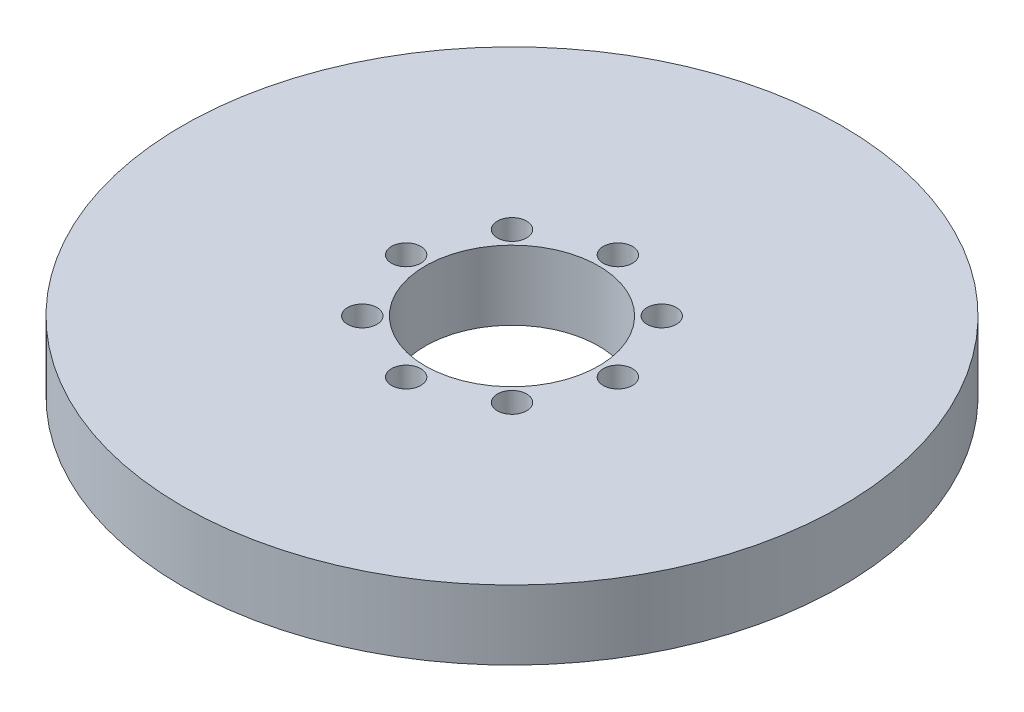
SolidWorks part; units mm, degrees
ref_plane "Front Plane" through (0, 0, 0) normal (0, 0, 1) x (1, 0, 0)
ref_plane "Top Plane" through (0, 0, 0) normal (0, 1, 0) x (1, 0, 0)
ref_plane "Right Plane" through (0, 0, 0) normal (1, 0, 0) x (0, 0, -1)
sketch "Sketch1" plane through (0, 0, 0) normal (0, 1, 0) x (1, 0, 0)
  circle A0 centre (0, 0) radius 47.5
  dimension "FLANGE_OD" = 95
extrude "Boss-Extrude1" add sketch "Sketch1" along normal blind 10
sketch "Sketch2" plane through (0, 0, 0) normal (0, 1, 0) x (1, 0, 0)
  circle A0 centre (0, 0) radius 12.5
  dimension "BORE_D" = 25
extrude "Cut-Extrude1" cut sketch "Sketch2" along normal through all
sketch "Sketch3" plane through (0, 10, 0) normal (0, 1, 0) x (1, 0, 0)
  circle A0 centre (0, 0) radius 15.2597 construction
  circle A1 centre (-15.2597, 0) radius 2.11
  dimension "BOLT_D" = 4.2201
  dimension "BOLT_PCD" = 30.5193
extrude "Cut-Extrude2" cut sketch "Sketch3" against normal blind 7.1757
pattern_circular "CirPattern1" count 8 over 360 about axis through (0, 0, 0) along (0, 1, 0) of "Cut-Extrude2"
